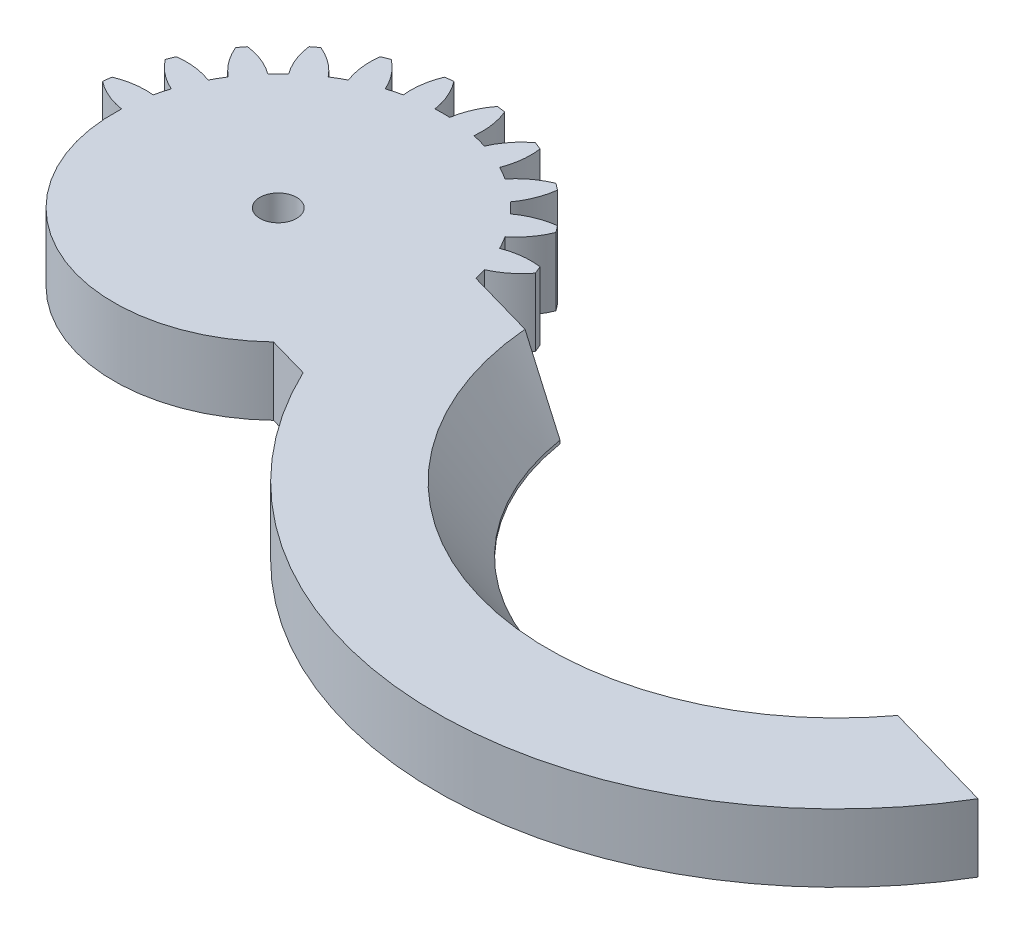
SolidWorks part; units mm, degrees
ref_plane "Front Plane" through (0, 0, 0) normal (0, 0, 1) x (1, 0, 0)
ref_plane "Top Plane" through (0, 0, 0) normal (0, 1, 0) x (1, 0, 0)
ref_plane "Right Plane" through (0, 0, 0) normal (1, 0, 0) x (0, 0, -1)
ref_plane "Plane1" through (0, 4, 0) normal (0, 1, 0) x (1, 0, 0)
sketch "Sketch1" plane through (0, 4, 0) normal (0, 1, 0) x (1, 0, 0)
  arc A0 (-24.5622, 2.2179) -> (-24.6437, 1.5991) centre (-10.1063, 0) ccw
  arc A1 (-24.6437, 1.5991) -> (-22.1869, 0.5427) centre (-21.3486, 5.8773) ccw
  arc A2 (-22.1869, 0.5427) -> (1.3057, -4) centre (-10.1063, 0) ccw
  arc A3 (1.3057, -4) -> (1.4221, 3.6509) centre (-10.1063, 0) ccw
  arc A4 (2.0816, 4) -> (3.5217, 5.3071) centre (-0.7683, 8.5867) ccw
  arc A5 (3.5217, 5.3071) -> (3.2829, 5.8838) centre (-10.1063, 0) ccw
  arc A6 (3.2829, 5.8838) -> (0.6271, 5.5703) centre (2.5684, 0.5313) ccw
  arc A7 (0.6271, 5.5703) -> (0.0844, 6.5103) centre (-10.1063, 0) ccw
  arc A8 (0.0844, 6.5103) -> (1.6838, 8.6535) centre (-3.3089, 10.711) ccw
  arc A9 (1.6838, 8.6535) -> (1.3038, 9.1487) centre (-10.1063, 0) ccw
  arc A10 (1.3038, 9.1487) -> (-1.1803, 8.1585) centre (1.999, 3.7936) ccw
  arc A11 (-1.1803, 8.1585) -> (-1.9479, 8.926) centre (-10.1063, 0) ccw
  arc A12 (-1.9479, 8.926) -> (-0.9576, 11.4102) centre (-6.3127, 12.1053) ccw
  arc A13 (-0.9576, 11.4102) -> (-1.4528, 11.7901) centre (-10.1063, 0) ccw
  arc A14 (-1.4528, 11.7901) -> (-3.596, 10.1907) centre (0.6046, 6.7975) ccw
  arc A15 (-3.596, 10.1907) -> (-4.5361, 10.7334) centre (-10.1063, 0) ccw
  arc A16 (-4.5361, 10.7334) -> (-4.2225, 13.3892) centre (-9.5751, 12.6747) ccw
  arc A17 (-4.2225, 13.3892) -> (-4.7992, 13.6281) centre (-10.1063, 0) ccw
  arc A18 (-4.7992, 13.6281) -> (-6.4554, 11.5285) centre (-1.5196, 9.3381) ccw
  arc A19 (-6.4554, 11.5285) -> (-7.5039, 11.8094) centre (-10.1063, 0) ccw
  arc A20 (-7.5039, 11.8094) -> (-7.8884, 14.4558) centre (-12.8736, 12.3803) ccw
  arc A21 (-7.8884, 14.4558) -> (-8.5072, 14.5373) centre (-10.1063, 0) ccw
  arc A22 (-8.5072, 14.5373) -> (-9.5636, 12.0806) centre (-4.2291, 11.2423) ccw
  arc A23 (-9.5636, 12.0806) -> (-10.6491, 12.0806) centre (-10.1063, 0) ccw
  arc A24 (-10.6491, 12.0806) -> (-11.7054, 14.5373) centre (-15.9836, 11.2423) ccw
  arc A25 (-11.7054, 14.5373) -> (-12.3243, 14.4558) centre (-10.1063, 0) ccw
  arc A26 (-12.3243, 14.4558) -> (-12.7088, 11.8094) centre (-7.3391, 12.3803) ccw
  arc A27 (-12.7088, 11.8094) -> (-13.7573, 11.5285) centre (-10.1063, 0) ccw
  arc A28 (-13.7573, 11.5285) -> (-15.4135, 13.6281) centre (-18.6931, 9.3381) ccw
  arc A29 (-15.4135, 13.6281) -> (-15.9901, 13.3892) centre (-10.1063, 0) ccw
  arc A30 (-15.9901, 13.3892) -> (-15.6766, 10.7334) centre (-10.6376, 12.6747) ccw
  arc A31 (-15.6766, 10.7334) -> (-16.6166, 10.1907) centre (-10.1063, 0) ccw
  arc A32 (-16.6166, 10.1907) -> (-18.7599, 11.7901) centre (-20.8173, 6.7975) ccw
  arc A33 (-18.7599, 11.7901) -> (-19.255, 11.4102) centre (-10.1063, 0) ccw
  arc A34 (-19.255, 11.4102) -> (-18.2648, 8.926) centre (-13.9, 12.1053) ccw
  arc A35 (-18.2648, 8.926) -> (-19.0324, 8.1585) centre (-10.1063, 0) ccw
  arc A36 (-19.0324, 8.1585) -> (-21.5165, 9.1487) centre (-22.2117, 3.7936) ccw
  arc A37 (-21.5165, 9.1487) -> (-21.8965, 8.6535) centre (-10.1063, 0) ccw
  arc A38 (-21.8965, 8.6535) -> (-20.2971, 6.5103) centre (-16.9038, 10.711) ccw
  arc A39 (-20.2971, 6.5103) -> (-20.8398, 5.5703) centre (-10.1063, 0) ccw
  arc A40 (-20.8398, 5.5703) -> (-23.4956, 5.8838) centre (-22.7811, 0.5313) ccw
  arc A41 (-23.4956, 5.8838) -> (-23.7344, 5.3071) centre (-10.1063, 0) ccw
  arc A42 (-23.7344, 5.3071) -> (-21.6348, 3.6509) centre (-19.4444, 8.5867) ccw
  arc A43 (-21.6348, 3.6509) -> (-21.9157, 2.6025) centre (-10.1063, 0) ccw
  arc A44 (-21.9157, 2.6025) -> (-24.5622, 2.2179) centre (-22.4867, -2.7673) ccw
  arc A45 (2.0816, 4) -> (1.4221, 3.6509) centre (-0.7683, 8.5867) cw
  dimension "D4" = 5.4
  dimension "D5" = 14.625
  dimension "D7" = 5.4
  dimension "D8" = 12.0927
  dimension "D9" = 5.4
  dimension "D10" = 0.0844
  dimension "D11" = 5.4
  dimension "D12" = 0.6046
  dimension "D13" = 5.4
  dimension "D14" = 0.6271
  dimension "D15" = 5.4
  dimension "D16" = 1.3038
  dimension "D17" = 5.4
  dimension "D18" = 1.3057
  dimension "D19" = 5.4
  dimension "D20" = 1.6838
  dimension "D21" = 5.4
  dimension "D22" = 1.999
  dimension "D23" = 5.4
  dimension "D24" = 2.0816
  dimension "D25" = 5.4
  dimension "D26" = 2.5684
  dimension "D27" = 5.4
  dimension "D28" = 3.2829
  dimension "D29" = 5.4
  dimension "D30" = 3.5217
  dimension "D31" = 5.4
  dimension "D32" = 0.412
  dimension "D33" = 5.4
  dimension "D34" = 0.9576
  dimension "D35" = 5.4
  dimension "D36" = 1.4528
  dimension "D37" = 5.4
  dimension "D38" = 1.5196
  dimension "D39" = 5.4
  dimension "D40" = 1.9479
  dimension "D41" = 5.4
  dimension "D42" = 4.2225
  dimension "D43" = 5.4
  dimension "D44" = 4.2291
  dimension "D45" = 5.4
  dimension "D46" = 4.5361
  dimension "D47" = 5.4
  dimension "D48" = 4.7992
  dimension "D49" = 7.3391
  dimension "D50" = 7.5039
  dimension "D51" = 7.8884
  dimension "D52" = 8.5072
  dimension "D53" = 10.6376
  dimension "D54" = 10.6491
  dimension "D55" = 11.7054
  dimension "D56" = 12.3243
  dimension "D57" = 13.7573
  dimension "D58" = 13.9
  dimension "D59" = 15.4135
  dimension "D60" = 15.6766
  dimension "D61" = 16.6166
  dimension "D62" = 16.9038
  dimension "D63" = 18.2648
  dimension "D64" = 18.7599
  dimension "D65" = 19.0324
  dimension "D66" = 19.4444
  dimension "D67" = 20.2971
  dimension "D68" = 20.8398
  dimension "D69" = 21.3486
  dimension "D70" = 21.5165
  dimension "D71" = 21.6348
  dimension "D72" = 21.9157
  dimension "D73" = 22.1869
  dimension "D74" = 22.4867
  dimension "D75" = 22.7811
  dimension "D76" = 0.5313
extrude "Boss-Extrude1" add sketch "Sketch1" against normal blind 5
sketch "草图1" plane through (0, -1, 0) normal (0, -1, 0) x (1, 0, 0)
  circle A0 centre (-10.1063, 0) radius 1.35
  point P6 (-10.1063, 0)
  dimension "D1" = 2.7
extrude "切除-拉伸1" cut sketch "草图1" against normal through all
sketch "草图2" plane through (0, -1, 0) normal (0, -1, 0) x (1, 0, 0)
  circle A0 centre (-10.1063, 0) radius 2.265
  circle A1 centre (-10.1063, 0) radius 4.265
  dimension "D1" = 2
  dimension "D2" = 4.53
extrude "凸台-拉伸1" add sketch "草图2" along normal blind 3
ref_axis "基准轴1" through (-10.1063, 25.6119, 0) along (0, -1, 0)
ref_plane "基准面1" through (-5.0532, 0, 5.0532) normal (-0.7071, 0, 0.7071) x (0, -1, 0)
sketch "草图3" plane through (0, -1, 0) normal (0, -1, 0) x (1, 0, 0)
  line L1 (1.3168, 9.5917) -> (-1.7324, 8.7242)
  line L2 (-17.5354, -16.0451) -> (42.6423, 1.0743) construction
  line L3 (13.3937, 23.5001) -> (-23.5001, -13.3937) construction
  line L6 (1.661, -2.7865) -> (-1.7324, 8.7242)
  line L7 (1.661, -2.7865) -> (10.3175, -0.3239)
  line L9 (41.4655, 8.5371) -> (53.3333, 11.9132)
  arc A1 (1.4221, -3.6509) -> (-22.1869, -0.5427) centre (-10.1063, 0) ccw construction
  arc A6 (10.3175, -0.3239) -> (41.4655, 8.5371) centre (27.9437, -3.1072) cw
  arc A7 (1.3168, 9.5917) -> (53.3333, 11.9132) centre (27.9437, -3.1072) cw
  point P15 (0, 6.5396)
  dimension "D2" = 13.4
  dimension "D3" = 7.5
  dimension "D4" = 9
  dimension "D6" = 29.5
  dimension "D1" = 29.12
  dimension "D5" = 38.05
  dimension "D7" = 12
extrude "凸台-拉伸2" add sketch "草图3" against normal up to surface (5 mm away) up to face at (-10.1063, 4, -1.35)
ref_axis "基准轴2" through (27.9437, -0.0479, -3.1072) along (0, -1, 0)
ref_plane "基准面2" through (8.6061, 0, -14.5472) normal (0.5092, 0, -0.8607) x (-0.8607, 0, -0.5092)
sketch "草图5" plane through (8.6061, 0, -14.5472) normal (0.5092, 0, -0.8607) x (-0.8607, 0, -0.5092)
  line L0 (-43.7681, 4) -> (-39.9681, -1.2342)
  line L1 (-40.0348, 4) -> (-51.9681, 4) construction
  line L5 (-39.9681, 4) -> (-43.7681, 4)
  line L7 (-8.715, 4) -> (-40.0348, 4) construction
  line L8 (-39.9681, 4) -> (-39.9681, -1.2342)
  line L9 (-22.4681, -0.0479) -> (-22.4681, -5.0479) construction
  dimension "D1" = 54.02
  dimension "D2" = 17.5
  dimension "D3" = 3.8
revolve "切除-旋转1" cut sketch "草图5" angle 360 about axis through (27.9437, -0.0479, -3.1072) along (0, -1, 0)
